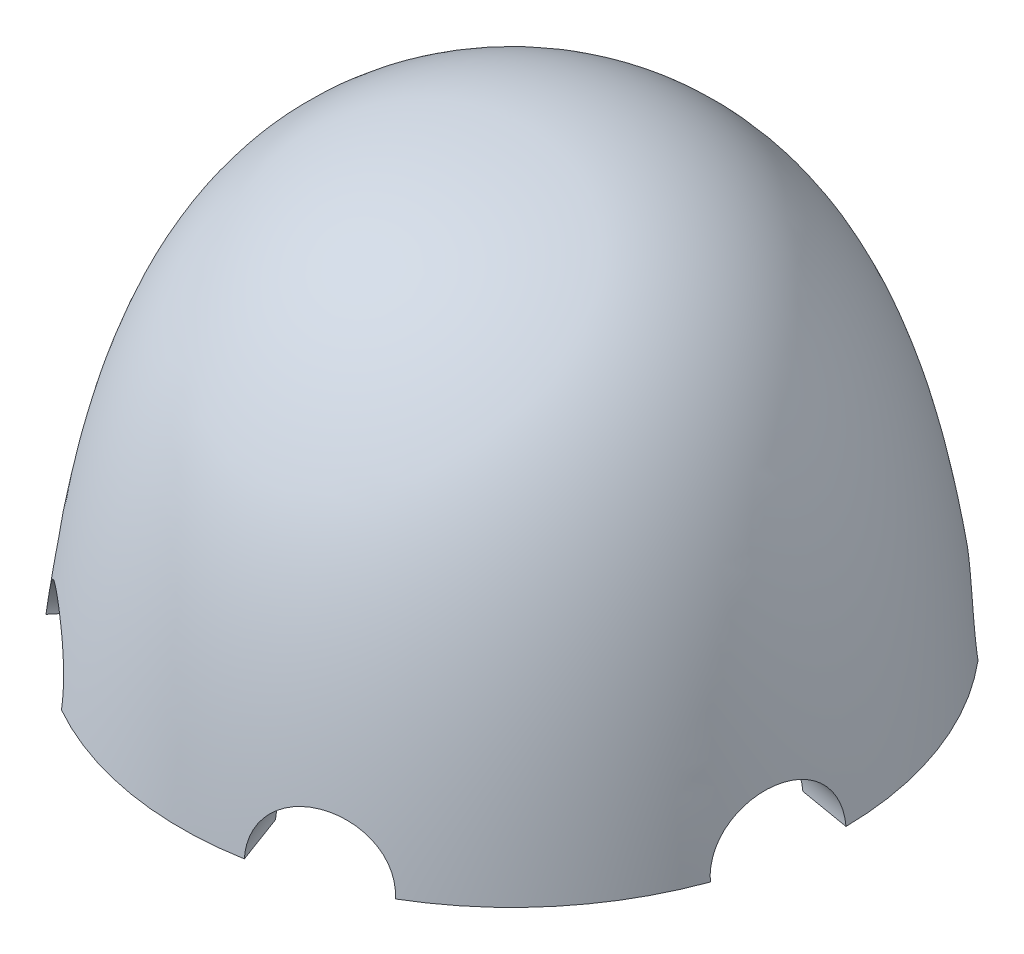
SolidWorks part; units mm, degrees
material "ABS"
ref_plane "前视基准面" through (0, 0, 0) normal (0, 0, 1) x (1, 0, 0)
ref_plane "上视基准面" through (0, 0, 0) normal (0, 1, 0) x (1, 0, 0)
ref_plane "右视基准面" through (0, 0, 0) normal (1, 0, 0) x (0, 0, -1)
sketch "草图1" plane through (0, 0, 0) normal (0, 0, 1) x (1, 0, 0)
  line L0 (-57.15, 0) -> (-48.2019, 0)
  line L1 (0, 0) -> (0, 67.31) construction
  line L2 (0, 67.31) -> (0, 76.2)
  line L3 (0, 76.2) -> (29.0141, 76.2) construction
  spline S0 degree 1 poles (-48.3166, -1.0012) (0, 67.31) knots 0 0 1 1 construction
  spline S1 degree 3 poles (-57.15, 0) (-53.2726, 34.209) (-44.696, 76.2) (0, 76.2) knots 0 0 0 0 1 1 1 1
  spline S2 degree 3 poles (-48.3166, -1.0012) (-48.0768, 1.1137) (-47.5705, 5.3223) (-46.3593, 13.8611) (-44.3859, 24.4358) (-40.986, 36.3818) (-36.3376, 46.9329) (-31.3387, 54.0999) (-26.5975, 58.7306) (-22.614, 61.6578) (-18.1088, 64.0391) (-13.812, 65.5483) (-9.9807, 66.4363) (-6.8971, 66.9301) (-4.1355, 67.1869) (-1.8183, 67.2921) (-0.6013, 67.31) (0, 67.31) knots 0 0 0 0 0.0625 0.125 0.25 0.375 0.5 0.625 0.6875 0.75 0.8125 0.875 0.90625 0.9375 0.96875 0.984375 1 1 1 1 only from (-48.2019, 0) to (0, 67.31)
  point P4 (0, 0)
  point P9 (0, 0)
  point P10 (0, 0)
  dimension "D4" = 8.89
  dimension "D1" = 114.3
  dimension "D2" = 76.2
revolve "旋转1" add sketch "草图1" angle 360 about L1
ref_plane "基准面1" through (0, 34.925, 0) normal (0, -1, 0) x (-1, 0, 0)
sketch "草图2" plane through (0, 34.925, 0) normal (0, -1, 0) x (-1, 0, 0)
  circle A0 centre (0, 53.975) radius 1.651
  circle A1 centre (0, 0) radius 53.975 construction
  point P2 (0, 0)
  point P3 (1.2025, 53.9464)
  dimension "D1" = 3.302
  dimension "D2" = 107.95
extrude "切除-拉伸2" cut sketch "草图2" along normal through all
sketch "草图3" plane through (0, 34.925, 0) normal (0, -1, 0) x (-1, 0, 0)
  circle A7 centre (0, 53.975) radius 3.175
  point P2 (0, 53.975)
  point P14 (16.2422, 43.8311)
  point P20 (3.8681, 8.2327)
  dimension "D1" = 6.35
extrude "切除-拉伸3" cut sketch "草图3" along normal blind 26
ref_axis "基准轴1" through (-50.6118, 8.925, 18.7548) along (0, 1, 0)
ref_axis "基准轴2" through (-41.5481, 8.925, -34.4537) along (0, 1, 0)
ref_plane "基准面2" through (-46.08, 0, -7.8494) normal (0.9858, 0, 0.1679) x (0.1679, 0, -0.9858)
ref_plane "基准面3" through (-78.6311, 0, -13.3943) normal (0.9858, 0, 0.1679) x (0.1679, 0, -0.9858)
sketch "草图4" plane through (-78.6311, 0, -13.3943) normal (0.9858, 0, 0.1679) x (0.1679, 0, -0.9858)
  line L0 (-57.15, 0) -> (57.15, 0) construction
  line L1 (10.16, 0) -> (-10.16, 0)
  arc A0 (10.16, 0) -> (-10.16, 0) centre (0, 0) ccw
  dimension "D1" = 10.16
extrude "切除-拉伸6" cut sketch "草图4" along normal through all
pattern_circular "阵列(圆周)1" count 3 over 360 about axis through (0, 0, 0) along (0, -1, 0) of "切除-拉伸6"
